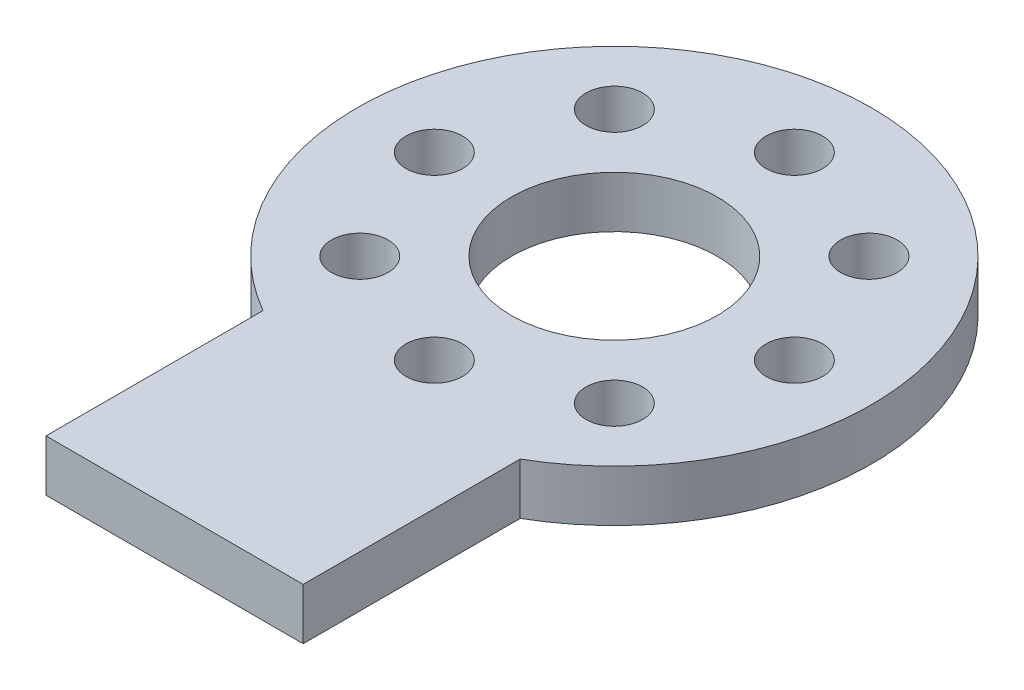
SolidWorks part; units mm, degrees
ref_plane "Front Plane" through (0, 0, 0) normal (0, 0, 1) x (1, 0, 0)
ref_plane "Top Plane" through (0, 0, 0) normal (0, 1, 0) x (1, 0, 0)
ref_plane "Right Plane" through (0, 0, 0) normal (1, 0, 0) x (0, 0, -1)
sketch "Sketch1" plane through (0, 0, 0) normal (0, 1, 0) x (1, 0, 0)
  line L0 (-12.5, -42.7479) -> (12.5, -42.7479)
  line L1 (12.5, -42.7479) -> (12.5, -21.6506)
  line L2 (-12.5, -42.7479) -> (-12.5, -21.6506)
  arc A0 (12.5, -21.6506) -> (-12.5, -21.6506) centre (0, 0) ccw
  point P5 (0, -42.7479)
  dimension "D1" = 50
  dimension "D2" = 25
extrude "Boss-Extrude1" add sketch "Sketch1" along normal blind 5
sketch "Sketch2" plane through (0, 5, 0) normal (0, 1, 0) x (1, 0, 0)
  circle A0 centre (0, 0) radius 17.5 construction
  point P3 (0, 17.5)
  point P6 (12.3744, 12.3744)
  point P7 (17.5, 0)
  point P8 (12.3744, -12.3744)
  point P9 (0, -17.5)
  point P10 (-12.3744, -12.3744)
  point P11 (-17.5, 0)
  point P12 (-12.3744, 12.3744)
  point P13 (0, 0)
  dimension "D2" = 35
  dimension "D1" = 8
hole_wizard "M5 Clearance Hole1" positions "Sketch4" profile "Sketch5" hole size "M5" standard "ANSI Metric" end condition through all
sketch "Sketch4" plane through (0, 5, 0) normal (0, 1, 0) x (1, 0, 0)
  point P0 (-12.3744, 12.3744)
  point P3 (0, 17.5)
  point P6 (12.3744, 12.3744)
  point P9 (17.5, 0)
  point P12 (12.3744, -12.3744)
  point P15 (0, -17.5)
  point P18 (-12.3744, -12.3744)
  point P21 (-17.5, 0)
sketch "Sketch5" plane through (-12.3744, 5, -12.3744) normal (1, 0, 0) x (0, 0, 1)
  line L0 (0, 0) -> (0, 5)
  line L1 (0, 5) -> (2.75, 5)
  line L2 (2.75, 5) -> (2.75, 0)
  line L5 (2.75, 0) -> (0, 0)
  line L11 (0, -6.35) -> (0, 107.95) construction
  dimension "Thru Hole Dia." = 5.5
  dimension "Thru Hole Depth" = 5
sketch "Sketch6" plane through (0, 5, 0) normal (0, 1, 0) x (1, 0, 0)
  circle A0 centre (0, 0) radius 10
  dimension "D1" = 20
extrude "Cut-Extrude1" cut sketch "Sketch6" against normal through all
